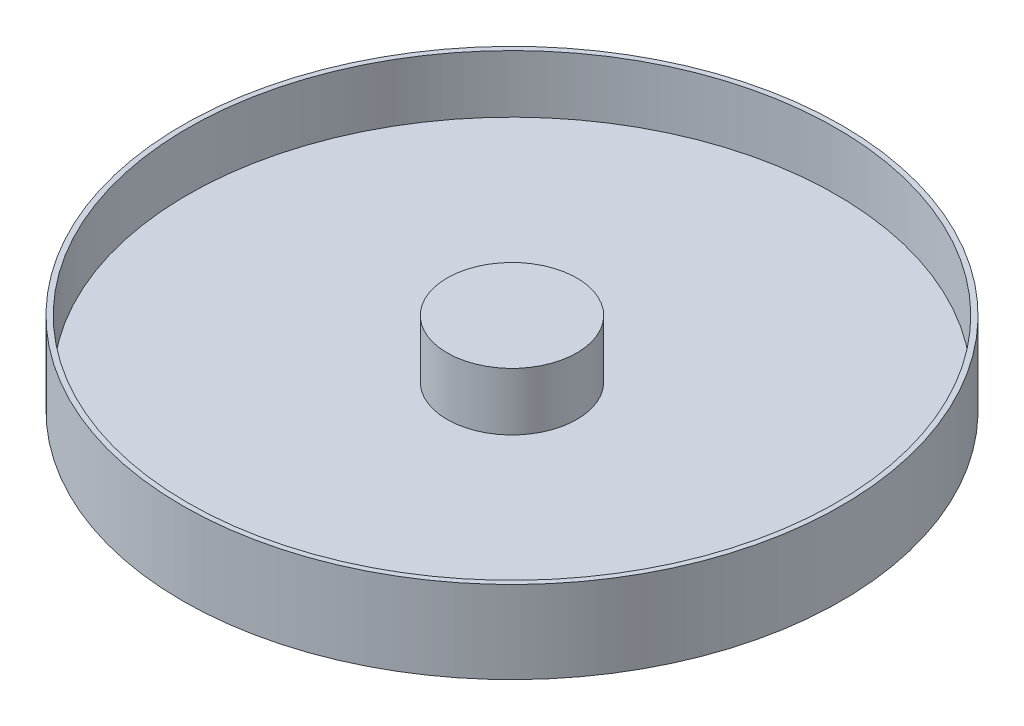
SolidWorks part; units mm, degrees
ref_plane "Front Plane" through (0, 0, 0) normal (0, 0, 1) x (1, 0, 0)
ref_plane "Top Plane" through (0, 0, 0) normal (0, 1, 0) x (1, 0, 0)
ref_plane "Right Plane" through (0, 0, 0) normal (1, 0, 0) x (0, 0, -1)
sketch "Sketch1" plane through (0, 0, 0) normal (0, 1, 0) x (1, 0, 0)
  line L0 (0, 0) -> (0, 13238.5693) construction
  line L1 (0, 0) -> (13238.5693, 0) construction
  circle A0 centre (0, 0) radius 78.75
  circle A1 centre (0, 0) radius 80
  circle A2 centre (0, 0) radius 15.75
  dimension "D1" = 31.5
  dimension "D2" = 63
  dimension "D3" = 160
extrude "Boss-Extrude1" add sketch "Sketch1" along normal blind 20 contours A1 A0 region at (-79.7737, 0, 0)
extrude "Boss-Extrude2" add sketch "Sketch1<3>" along normal blind 20 separate body contours A2 region at (0, 0, 0)
sketch "Sketch1<3>" plane through (0, 0, 0) normal (0, 1, 0) x (1, 0, 0) same geometry as "Sketch1"
extrude "Boss-Extrude3" add sketch "Sketch1<4>" along normal blind 6 contours A0 A2 region at (-76.5226, 0, 0)
sketch "Sketch1<4>" plane through (0, 0, 0) normal (0, 1, 0) x (1, 0, 0) same geometry as "Sketch1"
